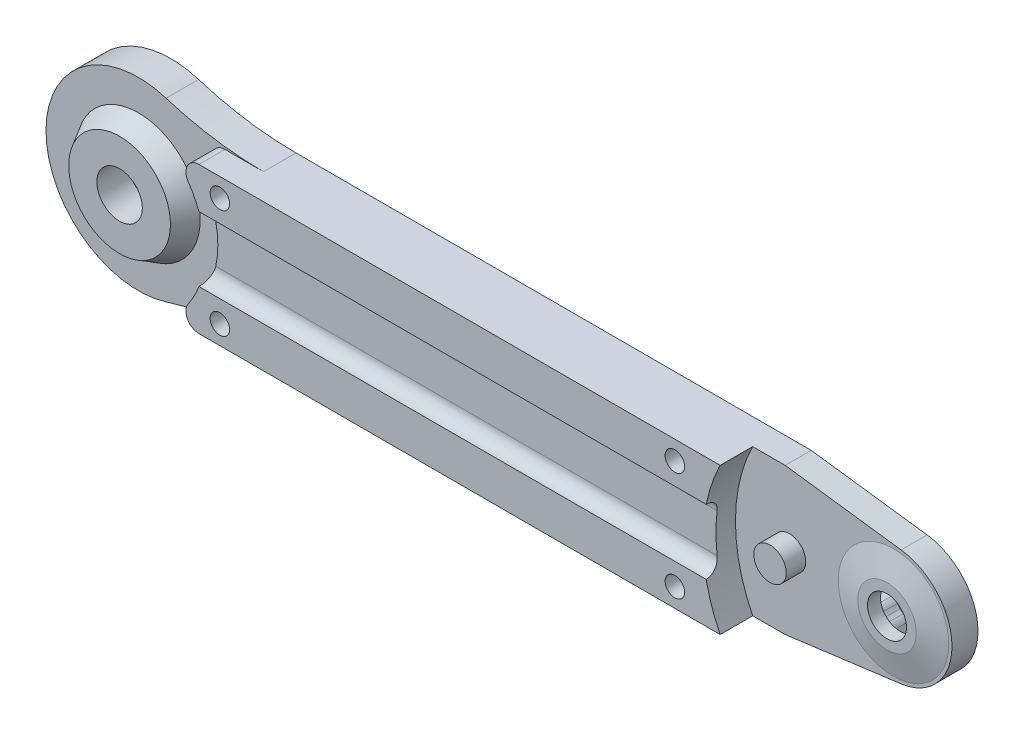
SolidWorks part; units mm, degrees
ref_plane "Front Plane" through (0, 0, 0) normal (0, 0, 1) x (1, 0, 0)
ref_plane "Top Plane" through (0, 0, 0) normal (0, 1, 0) x (1, 0, 0)
ref_plane "Right Plane" through (0, 0, 0) normal (1, 0, 0) x (0, 0, -1)
sketch "Sketch1" plane through (0, 0, 0) normal (0, 0, 1) x (1, 0, 0)
  line L0 (1.1747, 8.923) -> (-16.6713, 11.2725)
  line L1 (0, 0) -> (-37.632, 0) construction
  line L2 (1.1747, -8.923) -> (-16.6713, -11.2725)
  arc A0 (1.1747, -8.923) -> (1.1747, 8.923) centre (0, 0) ccw
  arc A1 (-16.6713, 11.2725) -> (-16.6713, -11.2725) centre (1.0468, 0) ccw
  dimension "D1" = 18
  dimension "D4" = 21
  dimension "D2" = 18
  dimension "D3" = 7.5
extrude "Boss-Extrude1" add sketch "Sketch1" along normal blind 4
sketch "Sketch2" plane through (0, 0, 4) normal (0, 0, 1) x (1, 0, 0)
  line L0 (0, 0) -> (-16, 0) construction
  circle A0 centre (-16, 0) radius 2.5
  dimension "D1" = 5
  dimension "D2" = 16
extrude "Boss-Extrude2" add sketch "Sketch2" along normal blind 3
sketch "Sketch3" plane through (0, 0, 4) normal (0, 0, 1) x (1, 0, 0)
  circle A0 centre (0, 0) radius 8.5
  dimension "D1" = 17
ref_plane "Plane1" through (0, 0, 5) normal (0, 0, 1) x (1, 0, 0)
sketch "Sketch5" plane through (0, 0, 5) normal (0, 0, 1) x (1, 0, 0)
  circle A0 centre (0, 0) radius 4.5
  dimension "D1" = 9
loft "Loft1" add profiles "Sketch5", "Sketch3" connector at (2.0278, 4.0172, 5) connector at (2.7886, 8.0295, 4)
sketch "Sketch6" plane through (0, 0, 5) normal (0, 0, 1) x (1, 0, 0)
  circle A0 centre (0, 0) radius 3
  dimension "D1" = 6
extrude "Cut-Extrude1" cut sketch "Sketch6" against normal through all
sketch "Sketch7" plane through (0, 0, 4) normal (0, 0, 1) x (1, 0, 0)
  line L0 (-16.6713, 11.2725) -> (-106.6713, 11.2725) construction
  line L2 (-106.6713, 11.2725) -> (-16.6713, 11.2725)
  line L3 (-106.6713, 11.2725) -> (-106.6713, -11.2725)
  line L4 (-106.6713, -11.2725) -> (-16.6713, -11.2725)
  line L5 (-16.6713, 11.2725) -> (-16.6713, -11.2725)
  dimension "D1" = 90
extrude "Boss-Extrude3" add sketch "Sketch7" against normal blind 4
sketch "Sketch8" plane through (0, 0, 4) normal (0, 0, 1) x (1, 0, 0)
  line L0 (-106.6713, -11.2725) -> (-16.6713, -11.2725) construction
  line L1 (-106.6713, 11.2725) -> (-21.6713, 11.2725)
  line L2 (-106.6713, 11.2725) -> (-106.6713, -11.2725)
  line L3 (-106.6713, -11.2725) -> (-21.6713, -11.2725)
  arc A0 (-21.6713, 11.2725) -> (-21.6713, -11.2725) centre (1.0234, 0) ccw
  dimension "D2" = 25.34
  dimension "D1" = 85
extrude "Boss-Extrude4" add sketch "Sketch8" along normal blind 5
sketch "Sketch9" plane through (0, 0, 0) normal (0, 0, -1) x (-1, 0, 0)
  line L0 (0, 0) -> (106.6713, 0) construction
  line L1 (23.0913, 5) -> (8.0913, 3.0252)
  line L2 (106.6713, 11.2725) -> (106.6713, -11.2725) construction
  line L3 (106.6713, 5) -> (23.0913, 5)
  line L8 (106.6713, 5) -> (106.6713, -5)
  line L11 (106.6713, -5) -> (23.0913, -5)
  line L12 (23.0913, -5) -> (8.0913, -3.0252)
  arc A1 (8.0913, 3.0252) -> (8.0913, -3.0252) centre (-0.9669, 0) cw
  dimension "D5" = 9.55
  dimension "D1" = 5
  dimension "D2" = 83.58
  dimension "D3" = 15
  dimension "D4" = 172.5
extrude "Cut-Extrude2" cut sketch "Sketch9" against normal blind 2
sketch "Sketch11" plane through (0, 0, 9) normal (0, 0, 1) x (1, 0, 0)
  line L0 (-106.6713, 0) -> (0, 0) construction
  line L1 (-106.6713, 11.2725) -> (-106.6713, -11.2725) construction
  line L3 (-106.6713, 5) -> (-23.8184, 5)
  line L4 (-106.6713, 5) -> (-106.6713, -5)
  line L5 (-106.6713, -5) -> (-23.8184, -5)
  arc A0 (-21.6713, 11.2725) -> (-21.6713, -11.2725) centre (1.0234, 0) ccw construction
  arc A1 (-23.8184, 5) -> (-23.8184, -5) centre (1.0234, 0) ccw
  dimension "D1" = 10
extrude "Cut-Extrude3" cut sketch "Sketch11" against normal blind 2
fillet "Fillet1" radius 2 2 edges at (-65.2449, -5, 7) (-65.2449, 5, 7)
sketch "Sketch12" plane through (0, 0, 0) normal (0, 0, -1) x (-1, 0, 0)
  line L0 (106.6713, 0) -> (83.0374, 0) construction
  line L1 (106.6713, -5) -> (106.6713, 5) construction
  line L2 (106.6713, 11.2725) -> (106.6713, 5) construction
  line L4 (106.6713, 6) -> (93.6713, 6)
  line L5 (106.6713, 6) -> (106.6713, -6)
  line L6 (106.6713, -6) -> (93.6713, -6)
  line L7 (93.6713, 6) -> (93.6713, -6)
  dimension "D1" = 12
  dimension "D2" = 13
extrude "Cut-Extrude4" cut sketch "Sketch12" against normal blind 2
sketch "Sketch13" plane through (0, 0, 0) normal (0, 0, -1) x (-1, 0, 0)
  line L0 (106.6713, 0) -> (115.1713, 0) construction
  line L1 (106.6713, -6) -> (106.6713, 6) construction
  circle A0 centre (115.1713, 0) radius 14.22
  dimension "D2" = 28.44
  dimension "D1" = 8.5
extrude "Boss-Extrude9" add sketch "Sketch13" against normal up to surface (9 mm away) up to face at (-64.7596, 8.1539, 9)
sketch "Sketch14" plane through (0, 0, 9) normal (0, 0, 1) x (1, 0, 0)
  circle A1 centre (-115.1713, 0) radius 14.22
extrude "Cut-Extrude5" cut sketch "Sketch14" against normal blind 4
fillet "Fillet2" radius 50 1 edges at (-106.503, -11.2725, 2.5)
fillet "Fillet3" radius 50 1 edges at (-106.503, 11.2725, 2.5)
fillet "Fillet4" radius 2 2 edges at (-106.503, -11.2725, 7) (-106.503, 11.2725, 7)
sketch "Sketch15" plane through (0, 0, 5) normal (0, 0, 1) x (1, 0, 0)
  circle A0 centre (-115.1713, 0) radius 9.5
  dimension "D1" = 19
extrude "Boss-Extrude10" add sketch "Sketch15" along normal blind 2.9 draft 30
sketch "Sketch16" plane through (0, 0, 7.9) normal (0, 0, 1) x (1, 0, 0)
  circle A0 centre (-115.1713, 0) radius 3.5
  dimension "D1" = 7
extrude "Cut-Extrude6" cut sketch "Sketch16" against normal through all
sketch "Sketch17" plane through (0, 0, 9) normal (0, 0, 1) x (1, 0, 0)
  line L1 (-98.64, 8.37) -> (-28.64, 8.37) construction
  line L2 (-98.64, 8.37) -> (-98.64, -8.37) construction
  line L3 (-98.64, -8.37) -> (-28.64, -8.37) construction
  line L4 (-28.64, 8.37) -> (-28.64, -8.37) construction
  circle A0 centre (-98.64, 8.37) radius 1.5
  circle A1 centre (-98.64, -8.37) radius 1.5
  circle A2 centre (-28.64, -8.37) radius 1.5
  circle A3 centre (-28.64, 8.37) radius 1.5
  point P4 (-63.64, -8.37)
  point P6 (-28.64, 0)
  dimension "D4" = 3
  dimension "D1" = 70
  dimension "D2" = 16.74
  dimension "D3" = 63.64
extrude "Cut-Extrude7" cut sketch "Sketch17" against normal through all
sketch "Sketch18" plane through (0, 0, 0) normal (0, 0, -1) x (-1, 0, 0)
  line L0 (115.14, -9) -> (115.14, 9) construction
  line L1 (140.7595, 0) -> (89.5204, 0) construction
  line L2 (115.14, 0) -> (140.7146, -25.5746) construction
  line L3 (116.63, -7.68) -> (117.42, -4.48)
  line L4 (122.82, -1.49) -> (119.62, -2.28)
  line L5 (122.82, 1.49) -> (119.62, 2.28)
  line L6 (116.63, 7.68) -> (117.42, 4.48)
  line L7 (113.65, 7.68) -> (112.86, 4.48)
  line L8 (107.46, 1.49) -> (110.66, 2.28)
  line L9 (107.46, -1.49) -> (110.66, -2.28)
  line L10 (113.65, -7.68) -> (112.86, -4.48)
  arc A0 (115.14, -9) -> (116.63, -7.68) centre (115.1408, -7.5) ccw
  arc A1 (117.42, -4.48) -> (118.21, -3.12) centre (119.4051, -4.7237) cw
  arc A2 (118.21, -3.12) -> (118.2383, -3.0984) centre (117.2916, -1.8876) ccw
  arc A3 (118.26, -3.07) -> (118.2383, -3.0984) centre (117.0276, -2.1516) cw
  arc A4 (119.62, -2.28) -> (118.26, -3.07) centre (119.8636, -4.2651) ccw
  arc A5 (124.14, 0) -> (122.82, -1.49) centre (122.64, -0.0008) cw
  arc A6 (124.14, 0) -> (122.82, 1.49) centre (122.64, 0.0008) ccw
  arc A7 (119.62, 2.28) -> (118.26, 3.07) centre (119.8636, 4.2651) cw
  arc A8 (118.26, 3.07) -> (118.2383, 3.0984) centre (117.0276, 2.1516) ccw
  arc A9 (118.21, 3.12) -> (118.2383, 3.0984) centre (117.2916, 1.8876) cw
  arc A10 (117.42, 4.48) -> (118.21, 3.12) centre (119.4051, 4.7237) ccw
  arc A11 (115.14, 9) -> (116.63, 7.68) centre (115.1408, 7.5) cw
  arc A12 (115.14, 9) -> (113.65, 7.68) centre (115.1391, 7.5) ccw
  arc A13 (112.86, 4.48) -> (112.07, 3.12) centre (110.8749, 4.7237) cw
  arc A14 (112.07, 3.12) -> (112.0416, 3.0984) centre (112.9884, 1.8876) ccw
  arc A15 (112.02, 3.07) -> (112.0416, 3.0984) centre (113.2523, 2.1516) cw
  arc A16 (110.66, 2.28) -> (112.02, 3.07) centre (110.4163, 4.2651) ccw
  arc A17 (106.14, 0) -> (107.46, 1.49) centre (107.64, 0.0008) cw
  arc A18 (106.14, 0) -> (107.46, -1.49) centre (107.64, -0.0008) ccw
  arc A19 (110.66, -2.28) -> (112.02, -3.07) centre (110.4163, -4.2651) cw
  arc A20 (112.02, -3.07) -> (112.0416, -3.0984) centre (113.2523, -2.1516) ccw
  arc A21 (112.07, -3.12) -> (112.0416, -3.0984) centre (112.9884, -1.8876) cw
  arc A22 (112.86, -4.48) -> (112.07, -3.12) centre (110.8749, -4.7237) ccw
  arc A23 (115.14, -9) -> (113.65, -7.68) centre (115.1391, -7.5) cw
  point P5 (115.14, 0)
  point P9 (115.14, 0)
  dimension "D7" = 1.5
  dimension "D10" = 2
  dimension "D1" = 9
  dimension "D2" = 45
  dimension "D3" = 1.49
  dimension "D4" = 0.79
  dimension "D5" = 1.32
  dimension "D6" = 3.2
  dimension "D8" = 0.79
  dimension "D9" = 1.36
extrude "Cut-Extrude8" cut sketch "Sketch18" against normal blind 3
sketch "Sketch19" plane through (0, 0, 0) normal (0, 0, -1) x (-1, 0, 0)
  line L0 (0, 7.25) -> (0, -7.25) construction
  line L1 (0, -7.25) -> (0, 0) construction
  line L2 (6.1605, 0) -> (-6.1605, 0) construction
  line L3 (-1.2, 6.33) -> (-1.8, 4.16)
  line L4 (1.2, -6.33) -> (1.8, -4.16)
  line L5 (6.33, -1.2) -> (4.16, -1.8)
  line L6 (6.33, 1.2) -> (4.16, 1.8)
  line L7 (1.2, 6.33) -> (1.8, 4.16)
  line L8 (-6.33, 1.2) -> (-4.16, 1.8)
  line L9 (-6.33, -1.2) -> (-4.16, -1.8)
  line L10 (-1.2, -6.33) -> (-1.8, -4.16)
  arc A0 (0, -7.25) -> (1.2, -6.33) centre (-0.0057, -6) ccw
  arc A1 (1.8, -4.16) -> (2.48, -3.3864) centre (3.5915, -5.049) cw
  arc A2 (2.48, -3.3864) -> (2.9857, -2.9857) centre (0.2569, -0.061) ccw
  arc A3 (3.3864, -2.48) -> (2.9857, -2.9857) centre (0.061, -0.2569) cw
  arc A4 (4.16, -1.8) -> (3.3864, -2.48) centre (5.049, -3.5915) ccw
  arc A5 (7.25, 0) -> (6.33, -1.2) centre (6, 0.0057) cw
  arc A6 (7.25, 0) -> (6.33, 1.2) centre (6, -0.0057) ccw
  arc A7 (4.16, 1.8) -> (3.3864, 2.48) centre (5.049, 3.5915) cw
  arc A8 (3.3864, 2.48) -> (2.9857, 2.9857) centre (0.061, 0.2569) ccw
  arc A9 (2.48, 3.3864) -> (2.9857, 2.9857) centre (0.2569, 0.061) cw
  arc A10 (1.8, 4.16) -> (2.48, 3.3864) centre (3.5915, 5.049) ccw
  arc A11 (0, 7.25) -> (1.2, 6.33) centre (-0.0057, 6) cw
  arc A12 (0, 7.25) -> (-1.2, 6.33) centre (0.0057, 6) ccw
  arc A13 (-1.8, 4.16) -> (-2.48, 3.3864) centre (-3.5915, 5.049) cw
  arc A14 (-2.48, 3.3864) -> (-2.9857, 2.9857) centre (-0.2569, 0.061) ccw
  arc A15 (-3.3864, 2.48) -> (-2.9857, 2.9857) centre (-0.061, 0.2569) cw
  arc A16 (-4.16, 1.8) -> (-3.3864, 2.48) centre (-5.049, 3.5915) ccw
  arc A17 (-7.25, 0) -> (-6.33, 1.2) centre (-6, -0.0057) cw
  arc A18 (-7.25, 0) -> (-6.33, -1.2) centre (-6, 0.0057) ccw
  arc A19 (-4.16, -1.8) -> (-3.3864, -2.48) centre (-5.049, -3.5915) cw
  arc A20 (-3.3864, -2.48) -> (-2.9857, -2.9857) centre (-0.061, -0.2569) ccw
  arc A21 (-2.48, -3.3864) -> (-2.9857, -2.9857) centre (-0.2569, -0.061) cw
  arc A22 (-1.8, -4.16) -> (-2.48, -3.3864) centre (-3.5915, -5.049) ccw
  arc A23 (0, -7.25) -> (-1.2, -6.33) centre (0.0057, -6) cw
  point P4 (0, 0)
  point P11 (0, 0)
  dimension "D5" = 1.25
  dimension "D10" = 2
  dimension "D13" = 4
  dimension "D1" = 7.25
  dimension "D3" = 0.92
  dimension "D4" = 1.2
  dimension "D6" = 2.17
  dimension "D7" = 0.6
  dimension "D8" = 0.68
  dimension "D9" = 1.03
extrude "Cut-Extrude9" cut sketch "Sketch19" against normal blind 3
